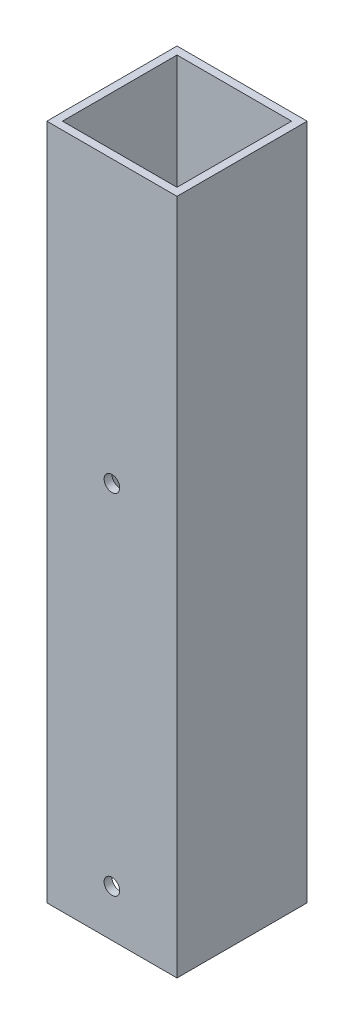
SolidWorks part; units mm, degrees
material "1060 Alloy"
ref_plane "Front Plane" through (0, 0, 0) normal (0, 0, 1) x (1, 0, 0)
ref_plane "Top Plane" through (0, 0, 0) normal (0, 1, 0) x (1, 0, 0)
ref_plane "Right Plane" through (0, 0, 0) normal (1, 0, 0) x (0, 0, -1)
sketch "Sketch3" plane through (0, 0, 0) normal (0, 1, 0) x (1, 0, 0)
  line L0 (0, 86.7063) -> (0, -87.1032) construction
  line L1 (-136.9048, 0) -> (130.9524, 0) construction
  line L7 (-12.5, 12.5) -> (12.5, 12.5)
  line L8 (-12.5, 12.5) -> (-12.5, -12.5)
  line L13 (-12.5, -12.5) -> (12.5, -12.5)
  line L14 (12.5, 12.5) -> (12.5, -12.5)
  line L15 (-12.5, 12.5) -> (12.5, -12.5) construction
  line L16 (-12.5, -12.5) -> (12.5, 12.5) construction
  line L17 (-11, 11) -> (11, 11)
  line L18 (-11, 11) -> (-11, -11)
  line L19 (-11, -11) -> (11, -11)
  line L20 (11, 11) -> (11, -11)
  line L21 (-11, 11) -> (11, -11) construction
  line L22 (-11, -11) -> (11, 11) construction
  point P5 (0, 0)
  point P10 (0, 0)
  dimension "D1" = 25
  dimension "D2" = 25
  dimension "D3" = 22
extrude "Boss-Extrude1" add sketch "Sketch3" along normal blind 65 and the other way blind 65
sketch "Sketch5" plane through (0, 0, -12.5) normal (0, 0, -1) x (-1, 0, 0)
  line L0 (-12.5, -65) -> (12.5, -65) construction
  circle A0 centre (0, -56) radius 1.5
  circle A1 centre (0, 11) radius 1.5
  dimension "D1" = 9
  dimension "D2" = 76
extrude "Cut-Extrude2" cut sketch "Sketch5" against normal blind 25
